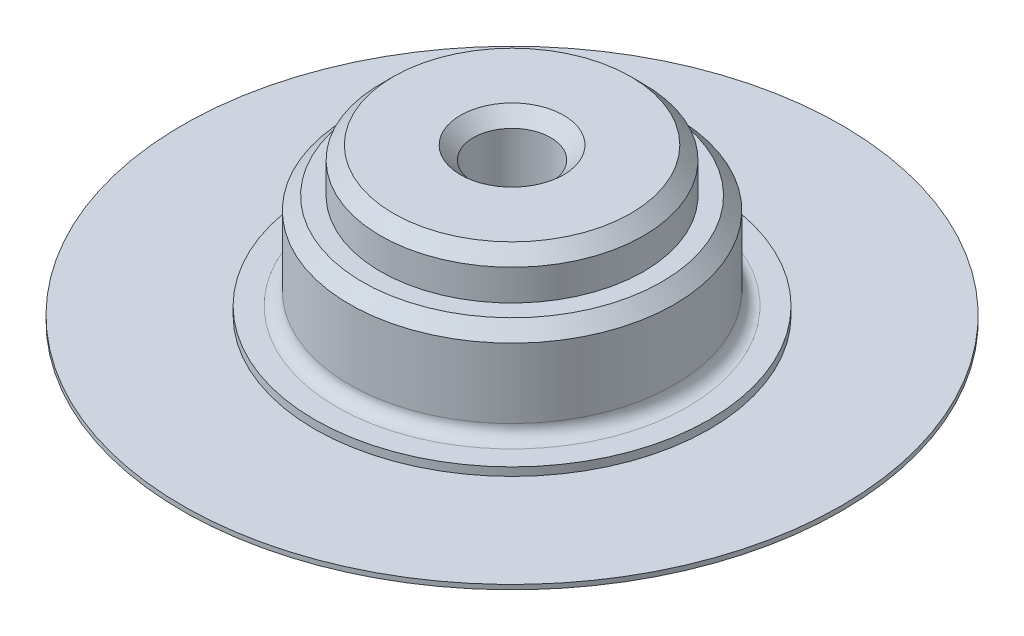
SolidWorks part; units mm, degrees
ref_plane "Front Plane" through (0, 0, 0) normal (0, 0, 1) x (1, 0, 0)
ref_plane "Top Plane" through (0, 0, 0) normal (0, 1, 0) x (1, 0, 0)
ref_plane "Right Plane" through (0, 0, 0) normal (1, 0, 0) x (0, 0, -1)
sketch "Sketch1" plane through (0, 0, 0) normal (0, 0, -1) x (0, -1, 0)
  line L0 (0, 1.5) -> (0, 12.78)
  line L14 (0, 0) -> (-10.9082, 0) construction
  line L15 (-5.4, 1.5) -> (0, 1.5)
  line L16 (-5.9, 2) -> (-5.4, 1.5)
  line L17 (-5.9, 4.6) -> (-5.9, 2)
  line L18 (-5.4, 5.1) -> (-5.9, 4.6)
  line L19 (-4.2, 5.1) -> (-5.4, 5.1)
  line L20 (-4.2, 5.8) -> (-4.2, 5.1)
  line L21 (-3.7, 6.3) -> (-4.2, 5.8)
  line L22 (-1, 6.3) -> (-3.7, 6.3)
  line L23 (-0.5, 7.65) -> (-0.5, 6.8)
  line L24 (-0.18, 7.65) -> (-0.5, 7.65)
  line L25 (-0.18, 12.78) -> (-0.18, 7.65)
  line L26 (0, 12.78) -> (-0.18, 12.78)
  arc A1 (-0.5, 6.8) -> (-1, 6.3) centre (-1, 6.8) cw
  dimension "D10" = 0.5
  dimension "D12" = 0.5
  dimension "D1" = 0.18
  dimension "D2" = 0.5
  dimension "D3" = 4.2
  dimension "D4" = 5.9
  dimension "D5" = 3
  dimension "D6" = 25.56
  dimension "D7" = 15.3
  dimension "D8" = 12.6
  dimension "D9" = 10.2
  dimension "D11" = 45
revolve "Revolve1" add sketch "Sketch1" angle 360 about L14
ref_axis "Axis1" through (0, 5.4, 0) along (0, -1, 0)
